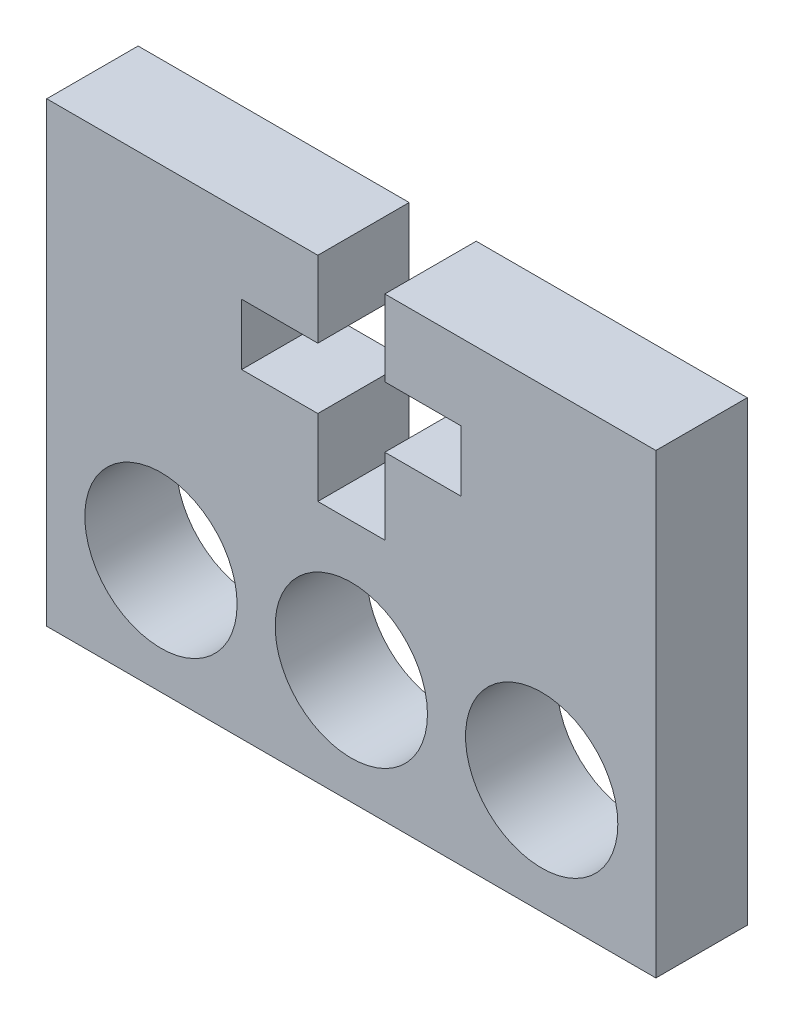
SolidWorks part; units mm, degrees
ref_plane "Front Plane" through (0, 0, 0) normal (0, 0, 1) x (1, 0, 0)
ref_plane "Top Plane" through (0, 0, 0) normal (0, 1, 0) x (1, 0, 0)
ref_plane "Right Plane" through (0, 0, 0) normal (1, 0, 0) x (0, 0, -1)
sketch "Sketch1" plane through (0, 0, 0) normal (0, 0, 1) x (1, 0, 0)
  line L0 (0, 7.5) -> (0, -7.5) construction
  line L1 (-10, -7.5) -> (10, -7.5)
  line L2 (-10, -7.5) -> (-10, 7.5)
  line L3 (-10, 7.5) -> (10, 7.5)
  line L4 (10, -7.5) -> (10, 7.5)
  line L5 (-10, -7.5) -> (10, 7.5) construction
  line L6 (-10, 7.5) -> (10, -7.5) construction
  line L7 (-1.1, 7.5) -> (-1.1, 5)
  line L8 (-1.1, 5) -> (-3.6, 5)
  line L9 (-3.6, 5) -> (-3.6, 3)
  line L10 (-3.6, 3) -> (-1.1, 3)
  line L11 (-1.1, 3) -> (-1.1, 0.5)
  line L12 (-1.1, 0.5) -> (1.1, 0.5)
  line L13 (1.1, 3) -> (1.1, 0.5)
  line L14 (3.6, 3) -> (1.1, 3)
  line L15 (3.6, 5) -> (3.6, 3)
  line L16 (1.1, 5) -> (3.6, 5)
  line L17 (1.1, 7.5) -> (1.1, 5)
  circle A0 centre (0, -3.75) radius 2.5
  circle A1 centre (-6.25, -3.75) radius 2.5
  circle A2 centre (6.25, -3.75) radius 2.5
  point P0 (0, 0)
  point P16 (0, 0.5)
  point P27 (0, 0)
  point P28 (0, 0)
  dimension "D7" = 5
  dimension "D1" = 15
  dimension "D2" = 2.5
  dimension "D3" = 2
  dimension "D4" = 2.5
  dimension "D5" = 1.1
  dimension "D6" = 2.5
  dimension "D8" = 20
  dimension "D9" = 3.75
  dimension "D10" = 6.25
  dimension "D11" = 6.25
extrude "Boss-Extrude1" add sketch "Sketch1" along normal blind 3 contours L3 L17 L16 L15 L14 L13 L12 L11 L10 L9 L8 L7 L2 L1 L4 A2 A1 A0 region at (-9.75, 0, 0)
